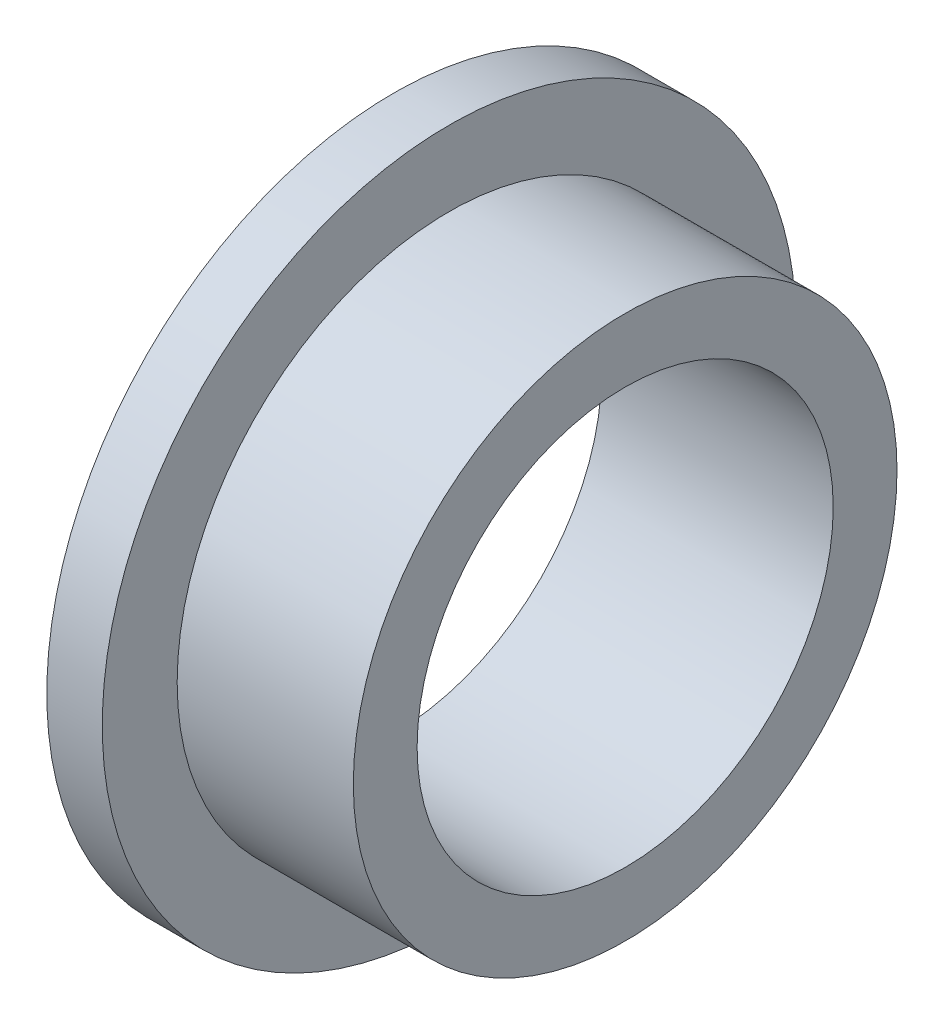
SolidWorks part; units mm, degrees
ref_plane "Front Plane" through (0, 0, 0) normal (0, 0, 1) x (1, 0, 0)
ref_plane "Top Plane" through (0, 0, 0) normal (0, 1, 0) x (1, 0, 0)
ref_plane "Right Plane" through (0, 0, 0) normal (1, 0, 0) x (0, 0, -1)
sketch "Sketch1" plane through (0, 0, 0) normal (1, 0, 0) x (0, 0, -1)
  circle A0 centre (0, 0) radius 12.5
  circle A1 centre (0, 0) radius 7.5
  dimension "D1" = 25
  dimension "D2" = 15
extrude "Boss-Extrude1" add sketch "Sketch1" along normal blind 2
sketch "Sketch2" plane through (2, 0, 0) normal (1, 0, 0) x (0, 0, -1)
  circle A0 centre (0, 0) radius 9.8
  circle A1 centre (0, 0) radius 7.5
  dimension "D1" = 19.6
extrude "Boss-Extrude2" add sketch "Sketch2" along normal blind 6.35
